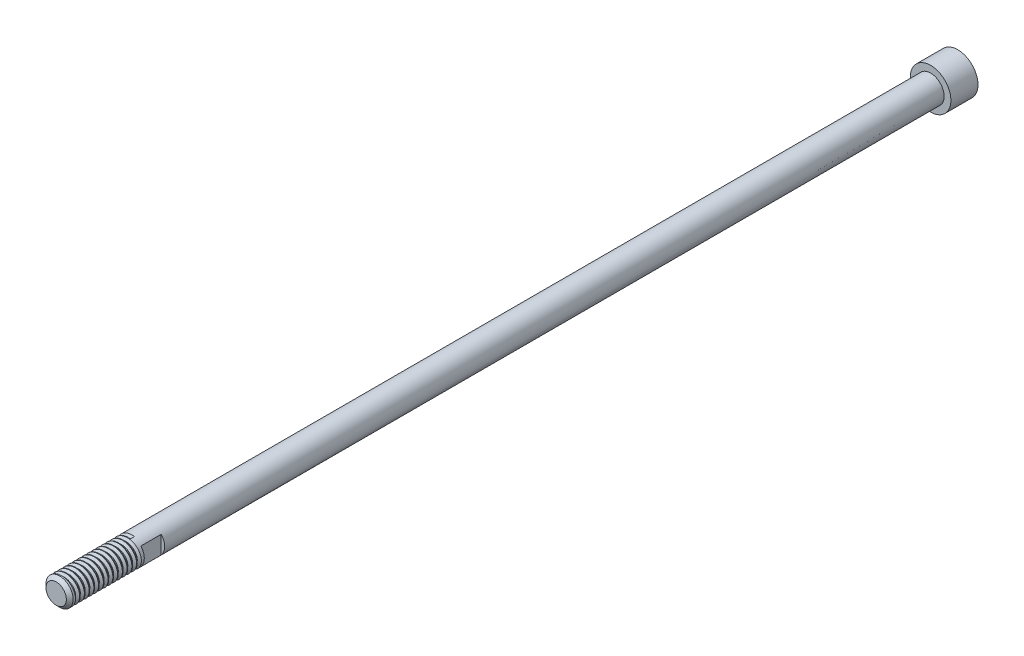
SolidWorks part; units mm, degrees
ref_plane "Front Plane" through (0, 0, 0) normal (0, 0, 1) x (1, 0, 0)
ref_plane "Top Plane" through (0, 0, 0) normal (0, 1, 0) x (1, 0, 0)
ref_plane "Right Plane" through (0, 0, 0) normal (1, 0, 0) x (0, 0, -1)
sketch "Sketch1" plane through (0, 0, 0) normal (0, 0, 1) x (1, 0, 0)
  circle A0 centre (0, 0) radius 2.99
  dimension "D1" = 5.98
extrude "Boss-Extrude1" add sketch "Sketch1" along normal blind 4
sketch "Sketch2" plane through (0, 0, 4) normal (0, 0, 1) x (1, 0, 0)
  circle A0 centre (0, 0) radius 2
  dimension "D1" = 4
extrude "Boss-Extrude2" add sketch "Sketch2" along normal blind 118
sketch "Sketch4" plane through (0, 0, 122) normal (0, 0, 1) x (1, 0, 0)
  line L1 (-3.0786, 1.9911) -> (-1.5, 1.9911)
  line L2 (-3.0786, 1.9911) -> (-3.0786, -2.0466)
  line L3 (-3.0786, -2.0466) -> (-1.5, -2.0466)
  line L4 (-1.5, 1.9911) -> (-1.5, -2.0466)
  line L5 (3.0786, 1.9911) -> (1.5, 1.9911)
  line L6 (3.0786, 1.9911) -> (3.0786, -2.0466)
  line L7 (3.0786, -2.0466) -> (1.5, -2.0466)
  line L8 (1.5, 1.9911) -> (1.5, -2.0466)
  dimension "D1" = 3
  dimension "D2" = 1.5
extrude "Cut-Extrude1" cut sketch "Sketch4" against normal blind 3
sketch "Sketch5" plane through (0, 0, 122) normal (0, 0, 1) x (1, 0, 0)
  circle A0 centre (0, 0) radius 2
extrude "Boss-Extrude3" add sketch "Sketch5" along normal blind 11
chamfer "Chamfer1" distance 0.5 angle 45 1 edges at (2, 0, 133)
thread "Thread2" pitch 0.7 start angle 0, offset 0, length 0, pitch 0.7, diameter 4
ref_plane "Plane2" through (-2, 0, 132.5) normal (0, -1, 0) x (-1, 0, 0)
sketch "Thread Profile2" plane through (-2, 0, 132.5) normal (0, -1, 0) x (-1, 0, 0)
  line L0 (0, 0) -> (0, 0.7) construction
  line L11 (0, 0) -> (0, 0.6125)
  line L12 (0, 0.6125) -> (-0.3789, 0.3937)
  line L13 (-0.3789, 0.3937) -> (-0.3789, 0.2187)
  line L15 (-0.3789, 0.2187) -> (0, 0)
  line L17 (-0.3789, 0.3062) -> (0, 0.3062) construction
  point P2 (0, 0)
  dimension "Pitch" = 0.7
  dimension "Profile_Angle" = 60
  dimension "Profile_Land" = 0.175
  dimension "Profile_Height" = 0.3789
